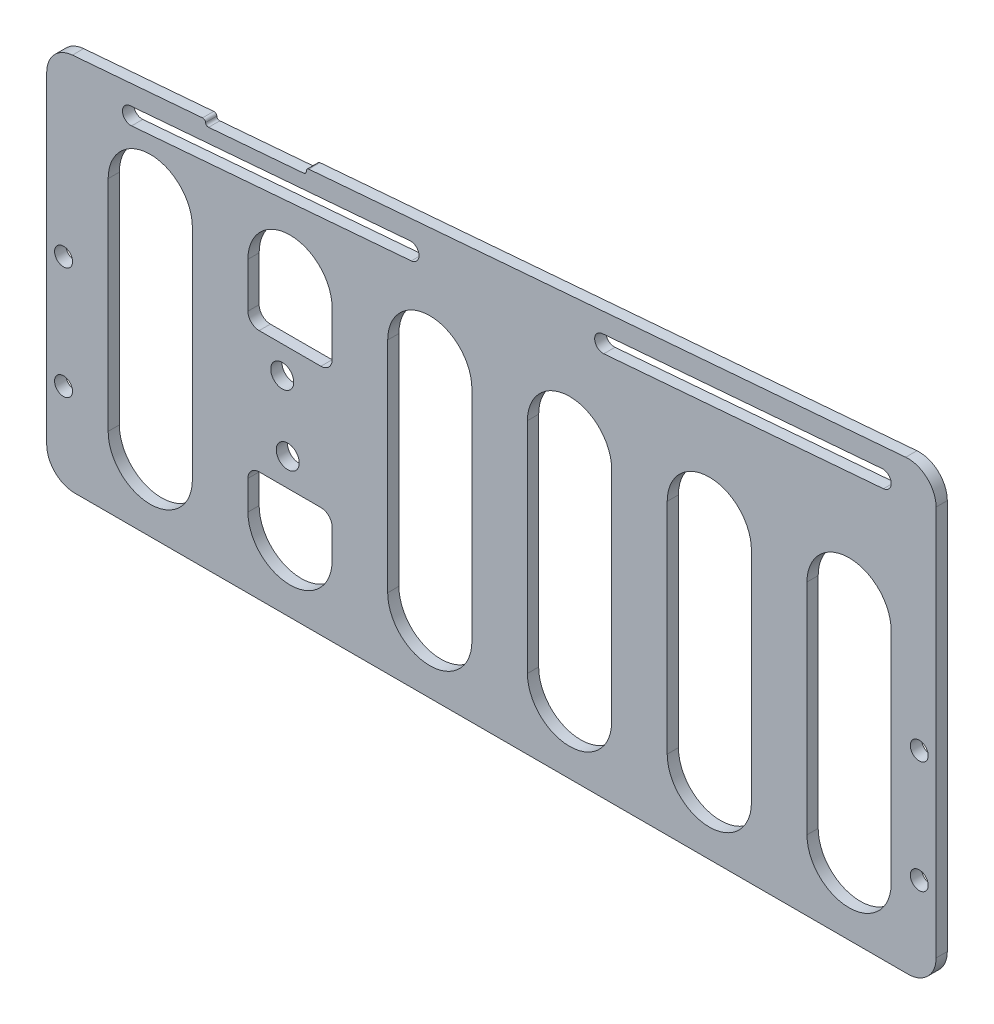
SolidWorks part; units mm, degrees
material "Thornel Mat VMA"
ref_plane "前视基准面" through (0, 0, 0) normal (0, 0, 1) x (1, 0, 0)
ref_plane "上视基准面" through (0, 0, 0) normal (0, 1, 0) x (1, 0, 0)
ref_plane "右视基准面" through (0, 0, 0) normal (1, 0, 0) x (0, 0, -1)
sketch "草图1" plane through (0, 0, 0) normal (0, 0, 1) x (1, 0, 0)
  line L1 (-79.225, -30) -> (79.225, -30)
  line L2 (-79.225, -30) -> (-79.225, 30)
  line L3 (-79.225, 30) -> (79.225, 30)
  line L4 (79.225, -30) -> (79.225, 30)
  line L5 (-79.225, -30) -> (79.225, 30) construction
  line L6 (-79.225, 30) -> (79.225, -30) construction
  point P0 (0, 0)
  dimension "D1" = 60
  dimension "D2" = 158.45
extrude "凸台-拉伸1" add sketch "草图1" along normal blind 2
sketch "草图2" plane through (0, 0, 2) normal (0, 0, 1) x (1, 0, 0)
  line L0 (-76.225, 5.5) -> (-76.225, 0) construction
  line L1 (-76.225, 0) -> (0, 0) construction
  line L2 (0, 0) -> (76.225, 0) construction
  line L3 (76.225, 0) -> (76.225, 5.5) construction
  line L4 (76.225, -14.5) -> (76.225, 0) construction
  line L5 (-76.225, 0) -> (-76.225, -14.5) construction
  line L6 (-79.225, 30) -> (-79.225, -30) construction
  line L7 (79.225, -30) -> (79.225, 30) construction
  circle A2 centre (-76.225, -14.5) radius 1.6
  circle A3 centre (-76.225, 5.5) radius 1.6
  circle A6 centre (76.225, -14.5) radius 1.6
  circle A7 centre (76.225, 5.5) radius 1.6
  dimension "D7" = 3.2
  dimension "D1" = 3
  dimension "D2" = 3
  dimension "D3" = 5.5
  dimension "D4" = 14.5
  dimension "D5" = 14.5
  dimension "D6" = 5.5
extrude "切除-拉伸1" cut sketch "草图2" against normal blind 10
sketch "草图3" plane through (0, 0, 0) normal (0, 0, -1) x (-1, 0, 0)
  line L0 (-79.225, 30) -> (-79.225, 50)
  line L1 (-79.225, 50) -> (79.225, 37)
  line L2 (79.225, 37) -> (79.225, 30)
  line L3 (-79.225, 30) -> (79.225, 30)
  dimension "D1" = 20
  dimension "D2" = 7
extrude "凸台-拉伸2" add sketch "草图3" against normal up to surface (2 mm away) up to face at (-74.625, 5.5, 2)
sketch "草图4" plane through (0, 0, 0) normal (0, 0, -1) x (-1, 0, 0)
  line L0 (-63.725, 21.5) -> (-63.725, -17.5) construction
  line L1 (-56.225, 21.5) -> (-56.225, -17.5)
  line L2 (-71.225, 21.5) -> (-71.225, -17.5)
  line L3 (79.225, -30) -> (-79.225, -30) construction
  arc A0 (-56.225, 21.5) -> (-71.225, 21.5) centre (-63.725, 21.5) ccw
  arc A1 (-71.225, -17.5) -> (-56.225, -17.5) centre (-63.725, -17.5) ccw
  circle A2 centre (-76.225, -14.5) radius 1.6 construction
  point P2 (-63.725, 2)
  dimension "D1" = 7.5
  dimension "D2" = 5
  dimension "D3" = 8
  dimension "D4" = 5
extrude "切除-拉伸2" cut sketch "草图4" against normal blind 10
pattern_linear "阵列(线性)1" count 6 spacing 24.9 along (-1, 0, 0) of "切除-拉伸2"
fillet "圆角1" radius 5 4 edges at (-79.225, -30, 1) (-79.225, 37, 1) (79.225, -30, 1) (79.225, 50, 1)
sketch "草图5" plane through (0, 0, 0) normal (0, 0, -1) x (-1, 0, 0)
  line L0 (-69.73, 44.2042) -> (-19.8975, 40.1157) construction
  line L1 (-69.6074, 45.6992) -> (-19.7748, 41.6107)
  line L2 (-69.8527, 42.7092) -> (-20.0201, 38.6207)
  line L3 (-71.225, 21.5) -> (-71.225, 44.3268) construction
  line L4 (74.6339, 37.3767) -> (-73.8161, 49.5562) construction
  line L5 (14.3924, 37.3024) -> (64.225, 33.2139) construction
  line L6 (14.5151, 38.7974) -> (64.3477, 34.7088)
  line L7 (14.2698, 35.8074) -> (64.1023, 31.7189)
  line L8 (79.225, 32.3934) -> (79.225, -25) construction
  arc A0 (-69.6074, 45.6992) -> (-69.8527, 42.7092) centre (-69.73, 44.2042) ccw
  arc A1 (-20.0201, 38.6207) -> (-19.7748, 41.6107) centre (-19.8975, 40.1157) ccw
  arc A4 (14.5151, 38.7974) -> (14.2698, 35.8074) centre (14.3924, 37.3024) ccw
  arc A5 (64.1023, 31.7189) -> (64.3477, 34.7088) centre (64.225, 33.2139) ccw
  point P2 (-44.8137, 42.1599)
  point P12 (39.3087, 35.2581)
  dimension "D2" = 1.5
  dimension "D1" = 5
  dimension "D3" = 50
  dimension "D4" = 5
  dimension "D5" = 15
extrude "切除-拉伸3" cut sketch "草图5" against normal blind 10
sketch "草图6" plane through (0, 0, 2) normal (0, 0, 1) x (1, 0, 0)
  line L0 (-38.6935, 40.3254) -> (-34.54, -10.3) construction
  line L1 (73.8161, 49.5562) -> (-74.6339, 37.3767) construction
  line L2 (-43.375, 11.5) -> (-28.375, 11.5)
  line L5 (-43.375, -17.5) -> (-43.375, 21.5) construction
  line L6 (-28.375, 21.5) -> (-28.375, -17.5) construction
  line L7 (-28.375, 11.5) -> (-28.375, -10.3)
  line L8 (-28.375, -10.3) -> (-43.375, -10.3)
  line L9 (-43.375, -10.3) -> (-43.375, 11.5)
  dimension "D1" = 11.5
  dimension "D2" = 10.3
extrude "凸台-拉伸3" add sketch "草图6" against normal up to surface (2 mm away) up to face at (44.8137, 42.1599, 0)
sketch "草图7" plane through (0, 0, 2) normal (0, 0, 1) x (1, 0, 0)
  line L0 (-40.0196, 40.2166) -> (-35.875, -10.3) construction
  line L1 (73.8161, 49.5562) -> (-74.6339, 37.3767) construction
  line L2 (-43.375, -10.3) -> (-28.375, -10.3) construction
  circle A0 centre (-37.2616, 6.6) radius 2.05
  circle A1 centre (-36.2803, -5.3598) radius 2.05
  dimension "D1" = 4.1
  dimension "D2" = 12
  dimension "D3" = 6.6
extrude "切除-拉伸4" cut sketch "草图7" against normal blind 10
fillet "圆角2" radius 2 4 edges at (-28.375, 11.5, 1) (-28.375, -10.3, 1) (-43.375, -10.3, 1) (-43.375, 11.5, 1)
sketch "草图8" plane through (-3.5451, 43.2091, 0) normal (-0.0818, 0.9967, 0) x (0.9967, 0.0818, 0)
  line L2 (-47.5764, -2) -> (-47.5764, 0)
  line L3 (-29.5764, 0) -> (-29.5764, -2)
  line L4 (77.6212, -2) -> (-71.3276, -2) construction
  line L5 (-71.3276, 0) -> (77.6212, 0) construction
  line L6 (-47.5764, 0) -> (-29.5764, 0)
  line L7 (-47.5764, -2) -> (-29.5764, -2)
  dimension "D1" = 29.5764
  dimension "D2" = 18
extrude "切除-拉伸5" cut sketch "草图8" against normal blind 1
fillet "圆角3" radius 0.5 4 edges at (-50.8804, 38.3222, 1) (-50.9622, 39.3188, 1) (-32.9407, 39.794, 1) (-33.0225, 40.7907, 1)
